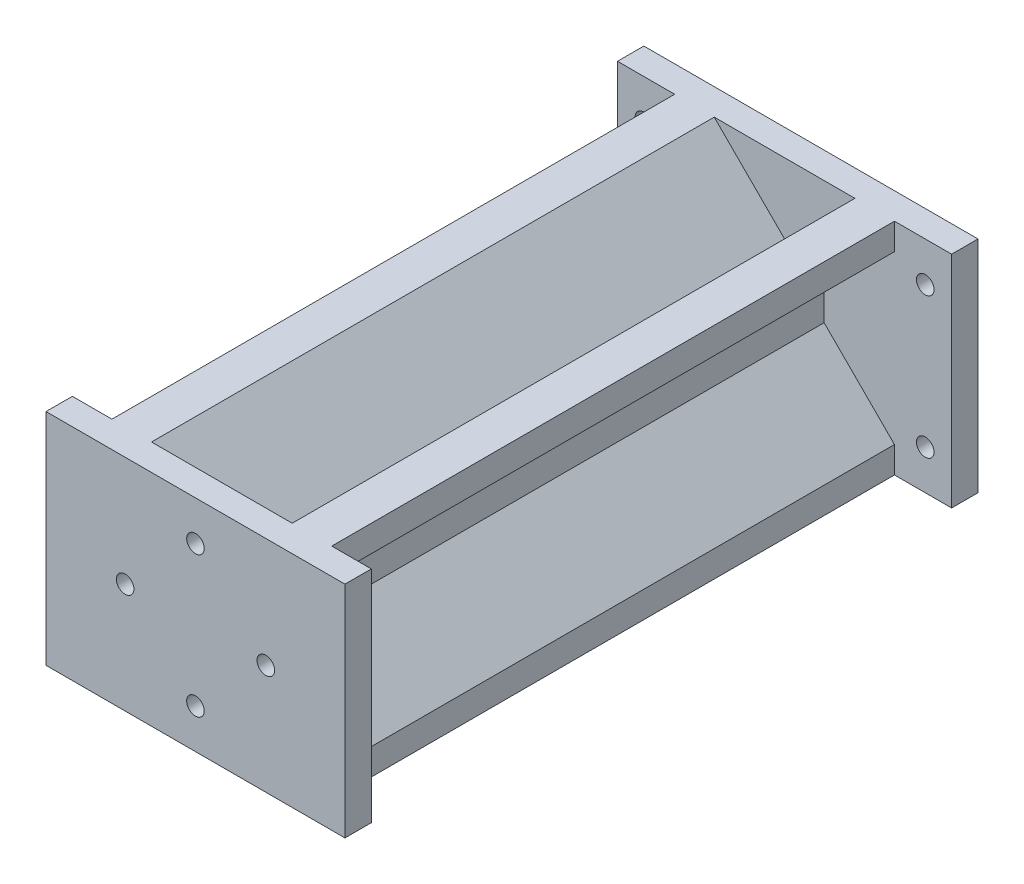
SolidWorks part; units mm, degrees
ref_plane "前视基准面" through (0, 0, 0) normal (0, 0, 1) x (1, 0, 0)
ref_plane "上视基准面" through (0, 0, 0) normal (0, 1, 0) x (1, 0, 0)
ref_plane "右视基准面" through (0, 0, 0) normal (1, 0, 0) x (0, 0, -1)
sketch "草图1" plane through (0, 0, 0) normal (0, 0, 1) x (1, 0, 0)
  line L0 (-45.6567, 0) -> (41.5448, 0) construction
  line L1 (-12.5, 12.5) -> (12.5, 12.5)
  line L2 (-12.5, 12.5) -> (-12.5, -12.5)
  line L3 (-12.5, -12.5) -> (12.5, -12.5)
  line L4 (12.5, 12.5) -> (12.5, -12.5)
  line L5 (0, 58.7621) -> (0, -33.7621) construction
  point P9 (0, 12.5)
  point P10 (12.5, 0)
  dimension "D1" = 25
  dimension "D2" = 25
extrude "凸台-拉伸1" add sketch "草图1" along normal blind 64
sketch "草图2" plane through (0, 0, 0) normal (0, 0, -1) x (-1, 0, 0)
  line L0 (-12.5, -12.5) -> (-12.5, 12.5) construction
  line L1 (-12.5, 9.5) -> (-4.5, 9.5)
  line L2 (-12.5, 9.5) -> (-12.5, -9.5)
  line L3 (-12.5, -9.5) -> (-4.5, -9.5)
  line L4 (-4.5, 9.5) -> (-4.5, -9.5)
  line L5 (-12.5, 12.5) -> (12.5, 12.5) construction
  line L6 (12.5, -12.5) -> (-12.5, -12.5) construction
  line L7 (-12.5, 9.5) -> (-4.5, 1.5)
  line L8 (-12.5, -9.5) -> (-4.5, -1.5)
  line M3 (-12.5, 12.5) -> (-12.5, -12.5)
  dimension "D1" = 8
  dimension "D2" = 3
  dimension "D3" = 3
  dimension "D4" = 45
  dimension "D5" = 45
extrude "切除-拉伸1" cut sketch "草图2" against normal blind 100 contours L8 L4 L7 M3 region at (9.4697, 0, 0)
mirror "镜向1" about plane through (0, 0, 0) normal (1, 0, 0) of "切除-拉伸1"
sketch "草图9" plane through (0, 0, 0) normal (0, 0, -1) x (-1, 0, 0)
  line L0 (0, 23.4554) -> (0, -17.569) construction
  line L1 (-8, 12.5) -> (0, 4.5)
  line L2 (-12.5, 12.5) -> (12.5, 12.5) construction
  line L3 (0, 4.5) -> (8, 12.5)
  line L4 (8, 12.5) -> (-8, 12.5)
  dimension "D1" = 45
  dimension "D2" = 45
  dimension "D3" = 16
extrude "切除-拉伸4" cut sketch "草图9" against normal up to surface (64 mm away) contours L1 L3 L4 up to face at (0, 0, 64)
mirror "镜向2" about plane through (0, 0, 0) normal (0, 1, 0) of "切除-拉伸4"
sketch "草图3" plane through (0, 0, 0) normal (0, 0, -1) x (-1, 0, 0)
  line L1 (-19, 12.5) -> (19, 12.5)
  line L2 (-19, 12.5) -> (-19, -12.5)
  line L3 (-19, -12.5) -> (19, -12.5)
  line L4 (19, 12.5) -> (19, -12.5)
  line L5 (0, 22.1705) -> (0, -27.6173) construction
  line L15 (12.5, -9.5) -> (4.5, -1.5)
  line L16 (4.5, 1.5) -> (12.5, 9.5)
  line L17 (12.5, 9.5) -> (12.5, 12.5)
  line L18 (12.5, 12.5) -> (8, 12.5)
  line L19 (-12.5, 12.5) -> (-12.5, 9.5)
  line L20 (-12.5, 9.5) -> (-4.5, 1.5)
  line L21 (-4.5, -1.5) -> (-12.5, -9.5)
  line L22 (-12.5, -9.5) -> (-12.5, -12.5)
  line L23 (-12.5, -12.5) -> (-8, -12.5)
  line L24 (12.5, -12.5) -> (12.5, -9.5)
  line L25 (12.5, -9.5) -> (4.5, -1.5)
  line L26 (4.5, 1.5) -> (12.5, 9.5)
  line L27 (12.5, 9.5) -> (12.5, 12.5)
  line L28 (12.5, 12.5) -> (8, 12.5)
  line L29 (-12.5, 12.5) -> (-12.5, 9.5)
  line L30 (-12.5, 9.5) -> (-4.5, 1.5)
  line L31 (-4.5, -1.5) -> (-12.5, -9.5)
  line L32 (-12.5, -9.5) -> (-12.5, -12.5)
  line L33 (-12.5, -12.5) -> (-8, -12.5)
  line L34 (12.5, -12.5) -> (12.5, -9.5)
  line L38 (4.5, -1.5) -> (4.5, 1.5)
  line L39 (4.5, -1.5) -> (4.5, 1.5)
  line L40 (-4.5, 1.5) -> (-4.5, -1.5)
  line L41 (-4.5, 1.5) -> (-4.5, -1.5)
  line L47 (-8, -12.5) -> (0, -4.5)
  line L48 (-8, -12.5) -> (0, -4.5)
  line L49 (0, -4.5) -> (8, -12.5)
  line L50 (0, -4.5) -> (8, -12.5)
  line L51 (8, -12.5) -> (12.5, -12.5)
  line L52 (8, -12.5) -> (12.5, -12.5)
  line L53 (8, 12.5) -> (0, 4.5)
  line L54 (8, 12.5) -> (0, 4.5)
  line L55 (0, 4.5) -> (-8, 12.5)
  line L56 (0, 4.5) -> (-8, 12.5)
  line L57 (-8, 12.5) -> (-12.5, 12.5)
  line L58 (-8, 12.5) -> (-12.5, 12.5)
  point P19 (0, 12.5)
  dimension "D2" = 38
  dimension "D1" = 0
extrude "凸台-拉伸2" add sketch "草图3" along normal blind 3 contours L1 L4 L3 L2
sketch "草图4" plane through (0, 0, -3) normal (0, 0, -1) x (-1, 0, 0)
  line L0 (0, 20.8506) -> (0, -22.3365) construction
  line L1 (-22.6868, 0) -> (23.8554, 0) construction
  circle A0 centre (-16, 8) radius 1
  dimension "D1" = 2
  dimension "D3" = 8
  dimension "D2" = 16
extrude "切除-拉伸2" cut sketch "草图4" against normal blind 3
pattern_linear "阵列(线性)1" count 2 spacing 32 along (-1, 0, 0) of "切除-拉伸2"
pattern_linear "阵列(线性)2" count 2 spacing 16 along (0, -1, 0) of "阵列(线性)1"
sketch "草图6" plane through (0, 0, -3) normal (0, 0, -1) x (-1, 0, 0)
  line L0 (0, 16.0793) -> (0, -21.177) construction
  line L1 (-4.95, 2.9) -> (4.95, 2.9)
  line L2 (-4.95, 2.9) -> (-4.95, -2.9)
  line L3 (-4.95, -2.9) -> (4.95, -2.9)
  line L4 (4.95, 2.9) -> (4.95, -2.9)
  line L5 (-23.7636, 0) -> (23.1777, 0) construction
  point P9 (0, -2.9)
  point P10 (4.95, 0)
  dimension "D1" = 9.9
  dimension "D2" = 5.8
extrude "凸台-拉伸3" add sketch "草图6" along normal blind 3
sketch "草图7" plane through (0, 0, 64) normal (0, 0, 1) x (1, 0, 0)
  line L0 (0, 16.9996) -> (0, -15.9877) construction
  line L1 (-17, 12.5) -> (17, 12.5)
  line L2 (-17, 12.5) -> (-17, -12.5)
  line L3 (-17, -12.5) -> (17, -12.5)
  line L4 (17, 12.5) -> (17, -12.5)
  line L12 (-4.5, 1.5) -> (-4.5, -1.5)
  line L13 (-4.5, -1.5) -> (-12.5, -9.5)
  line L14 (-12.5, -9.5) -> (-12.5, -12.5)
  line L15 (-12.5, -12.5) -> (-8, -12.5)
  line L16 (12.5, -12.5) -> (12.5, -9.5)
  line L17 (12.5, -9.5) -> (4.5, -1.5)
  line L18 (4.5, -1.5) -> (4.5, 1.5)
  line L19 (4.5, 1.5) -> (12.5, 9.5)
  line L20 (12.5, 9.5) -> (12.5, 12.5)
  line L21 (12.5, 12.5) -> (8, 12.5)
  line L22 (-12.5, 12.5) -> (-12.5, 9.5)
  line L23 (-12.5, 9.5) -> (-4.5, 1.5)
  line L24 (-4.5, 1.5) -> (-4.5, -1.5)
  line L25 (-4.5, -1.5) -> (-12.5, -9.5)
  line L26 (-12.5, -9.5) -> (-12.5, -12.5)
  line L27 (-12.5, -12.5) -> (-8, -12.5)
  line L28 (12.5, -12.5) -> (12.5, -9.5)
  line L29 (12.5, -9.5) -> (4.5, -1.5)
  line L30 (4.5, -1.5) -> (4.5, 1.5)
  line L31 (4.5, 1.5) -> (12.5, 9.5)
  line L32 (12.5, 9.5) -> (12.5, 12.5)
  line L33 (12.5, 12.5) -> (8, 12.5)
  line L34 (-12.5, 12.5) -> (-12.5, 9.5)
  line L35 (-12.5, 9.5) -> (-4.5, 1.5)
  line L46 (-8, -12.5) -> (0, -4.5)
  line L47 (-8, -12.5) -> (0, -4.5)
  line L48 (0, -4.5) -> (8, -12.5)
  line L49 (0, -4.5) -> (8, -12.5)
  line L50 (8, -12.5) -> (12.5, -12.5)
  line L51 (8, -12.5) -> (12.5, -12.5)
  line L52 (8, 12.5) -> (0, 4.5)
  line L53 (8, 12.5) -> (0, 4.5)
  line L54 (0, 4.5) -> (-8, 12.5)
  line L55 (0, 4.5) -> (-8, 12.5)
  line L56 (-8, 12.5) -> (-12.5, 12.5)
  line L57 (-8, 12.5) -> (-12.5, 12.5)
  point P17 (0, 12.5)
  dimension "D2" = 34
  dimension "D1" = 0
extrude "凸台-拉伸4" add sketch "草图7" along normal blind 3 contours L3 L4 L1 L2
sketch "草图8" plane through (0, 0, 67) normal (0, 0, 1) x (1, 0, 0)
  line L0 (0, 19.1963) -> (0, -19.5717) construction
  line L1 (-26.3315, 0) -> (26.9109, 0) construction
  circle A0 centre (0, 8) radius 1
  dimension "D1" = 2
  dimension "D2" = 8
extrude "切除-拉伸3" cut sketch "草图8" against normal blind 3
ref_axis "基准轴1" through (0, 0, -9.95) along (0, 0, 1)
pattern_circular "阵列(圆周)1" count 4 over 360 about axis through (0, 0, -9.95) along (0, 0, 1) of "切除-拉伸3"
